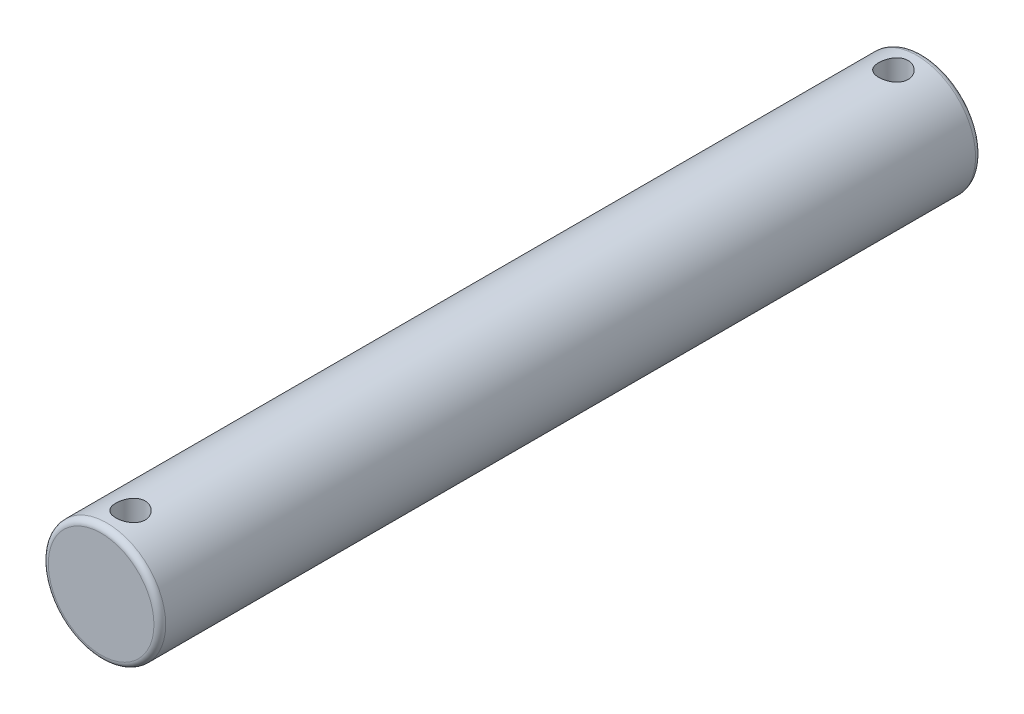
SolidWorks part; units mm, degrees
ref_plane "Front Plane" through (0, 0, 0) normal (0, 0, 1) x (1, 0, 0)
ref_plane "Top Plane" through (0, 0, 0) normal (0, 1, 0) x (1, 0, 0)
ref_plane "Right Plane" through (0, 0, 0) normal (1, 0, 0) x (0, 0, -1)
sketch "Sketch1" plane through (0, 0, 0) normal (0, 0, 1) x (1, 0, 0)
  circle A0 centre (0, 0) radius 10
  dimension "D1" = 20
extrude "Boss-Extrude1" add sketch "Sketch1" along normal blind 140
fillet "Fillet1" radius 1 2 edges at (10, 0, 0) (10, 0, 140)
sketch "Sketch2" plane through (0, 0, 0) normal (0, 1, 0) x (1, 0, 0)
  line L0 (9, 0) -> (-9, 0) construction
  line L1 (-9, -140) -> (9, -140) construction
  circle A0 centre (0, -5) radius 2.5
  circle A1 centre (0, -135) radius 2.5
  dimension "D1" = 5
  dimension "D2" = 5
  dimension "D3" = 5
  dimension "D4" = 5
extrude "Cut-Extrude1" cut sketch "Sketch2" against normal blind 140 and the other way blind 140
